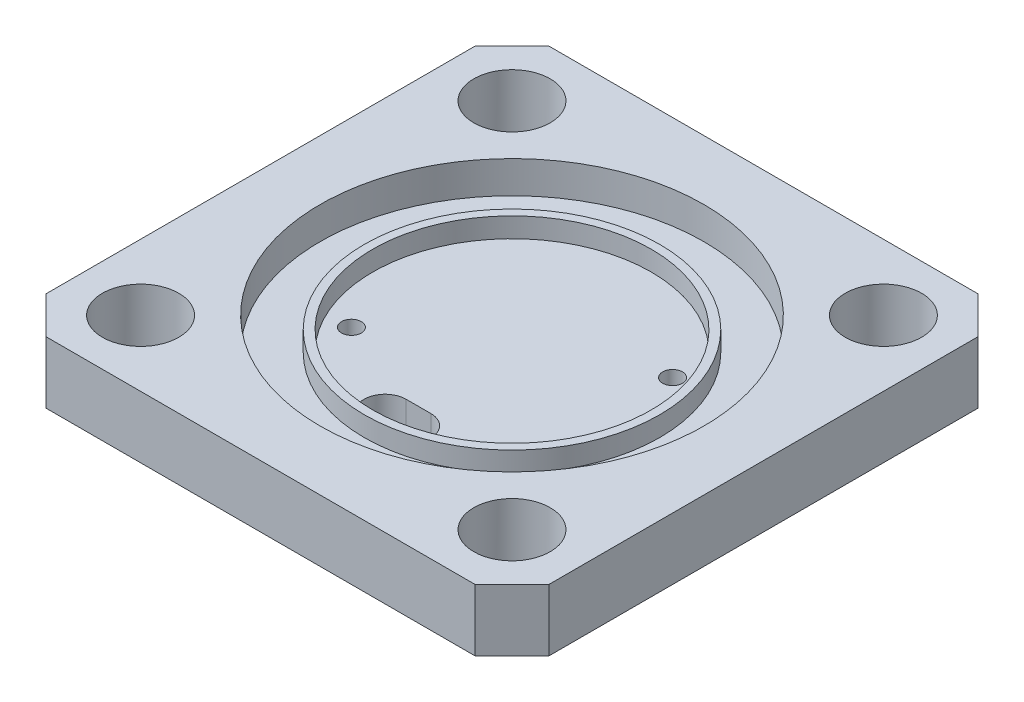
SolidWorks part; units mm, degrees
ref_plane "Front Plane" through (0, 0, 0) normal (0, 0, 1) x (1, 0, 0)
ref_plane "Top Plane" through (0, 0, 0) normal (0, 1, 0) x (1, 0, 0)
ref_plane "Right Plane" through (0, 0, 0) normal (1, 0, 0) x (0, 0, -1)
sketch "Sketch1" plane through (0, 0, 0) normal (0, 1, 0) x (1, 0, 0)
  line L1 (-20.32, -20.32) -> (20.32, -20.32)
  line L2 (-20.32, -20.32) -> (-20.32, 20.32)
  line L3 (-20.32, 20.32) -> (20.32, 20.32)
  line L4 (20.32, -20.32) -> (20.32, 20.32)
  line L5 (-20.32, -20.32) -> (20.32, 20.32) construction
  line L6 (-20.32, 20.32) -> (20.32, -20.32) construction
  point P0 (0, 0)
  dimension "D1" = 40.64
  dimension "D2" = 40.64
extrude "Boss-Extrude1" add sketch "Sketch1" along normal blind 5
sketch "Sketch2" plane through (0, 5, 0) normal (0, 1, 0) x (1, 0, 0)
  line L1 (-15, -15) -> (15, -15) construction
  line L2 (-15, -15) -> (-15, 15) construction
  line L3 (-15, 15) -> (15, 15) construction
  line L4 (15, -15) -> (15, 15) construction
  line L5 (-15, -15) -> (15, 15) construction
  line L6 (-15, 15) -> (15, -15) construction
  circle A0 centre (-15, 15) radius 3.085
  circle A1 centre (15, 15) radius 3.085
  circle A2 centre (15, -15) radius 3.085
  circle A3 centre (-15, -15) radius 3.085
  point P0 (0, 0)
  dimension "D3" = 6.17
  dimension "D1" = 30
  dimension "D2" = 30
  dimension "D4" = 2
  dimension "D5" = 2
extrude "Cut-Extrude1" cut sketch "Sketch2" against normal up to next contours A0 | A1 | A2 | A3
chamfer "Chamfer1" distance 3 angle 45 4 edges at (-20.32, 2.5, 20.32) (20.32, 2.5, 20.32) (20.32, 2.5, -20.32) (-20.32, 2.5, -20.32)
sketch "Sketch3" plane through (0, 5, 0) normal (0, 1, 0) x (1, 0, 0)
  circle A0 centre (0, 0) radius 11.25
  dimension "D1" = 22.5
extrude "Cut-Extrude2" cut sketch "Sketch3" against normal blind 2.6
ref_point "Point1"
sketch "Sketch4" plane through (0, 5, 0) normal (0, 1, 0) x (1, 0, 0)
  circle A0 centre (0, 0) radius 12000
  circle A1 centre (0, 0) radius 15.5
  circle A2 centre (0, 0) radius 11.925
  dimension "D1" = 24000
  dimension "D2" = 31
  dimension "D3" = 23.85
extrude "Cut-Extrude3" cut sketch "Sketch4" against normal blind 2.6 contours A1 A2 region at (-15.0616, 5, 0)
sketch "Sketch5" plane through (0, 2.4, 0) normal (0, 1, 0) x (1, 0, 0)
  line L0 (0, 0) -> (0, -11.25) construction
  line L1 (-1, -9.25) -> (1, -9.25) construction
  line L2 (-1, -11.25) -> (1, -11.25) construction
  line L3 (-1, -11.25) -> (-1, -7.25) construction
  line L4 (-1, -7.25) -> (1, -7.25) construction
  line L5 (1, -11.25) -> (1, -7.25) construction
  line L6 (-1, -11.25) -> (1, -7.25) construction
  line L7 (-1, -7.25) -> (1, -11.25) construction
  line L8 (-1, -7.55) -> (1, -7.55)
  line L9 (-1, -10.95) -> (1, -10.95)
  circle A0 centre (0, 0) radius 11.25 construction
  circle A1 centre (0, 0) radius 9.25 construction
  arc A2 (-1, -7.55) -> (-1, -10.95) centre (-1, -9.25) ccw
  arc A7 (1, -10.95) -> (1, -7.55) centre (1, -9.25) ccw
  point P6 (0, -9.25)
  point P14 (0, -9.25)
  dimension "D1" = 4
  dimension "D2" = 2
  dimension "D3" = 0
  dimension "D4" = 3.4
extrude "Cut-Extrude4" cut sketch "Sketch5" against normal through all contours L9 A7 L8 A2
sketch "Sketch6" plane through (0, 5, 0) normal (0, 1, 0) x (1, 0, 0)
  circle A3 centre (0, 0) radius 11.25 construction
  circle A4 centre (0, 0) radius 11.25
  circle A5 centre (0, 0) radius 11.925
  circle A8 centre (0, 0) radius 11.925
  dimension "D1" = 0
extrude "Cut-Extrude5" cut sketch "Sketch6" against normal blind 1
sketch "Sketch7" plane through (0, 2.4, 0) normal (0, 1, 0) x (1, 0, 0)
  line L0 (8.2431, 4.7273) -> (-8.2431, -4.7273) construction
  circle A0 centre (8.2431, 4.7273) radius 0.8
  circle A1 centre (0, 0) radius 11.25
  circle A2 centre (0, 0) radius 11.25 construction
  circle A3 centre (8.2431, 4.7273) radius 1
  circle A4 centre (8.2431, 4.7273) radius 1 construction
  circle A5 centre (-8.2431, -4.7273) radius 1
  circle A6 centre (-8.2431, -4.7273) radius 1 construction
  circle A7 centre (0, 0) radius 11
  circle A8 centre (0, 0) radius 11 construction
  circle A9 centre (-8.2431, -4.7273) radius 0.8
  dimension "D5" = 1.6
  dimension "D6" = 1.6
  dimension "D1" = 0
  dimension "D2" = 0
  dimension "D3" = 0
  dimension "D4" = 0
extrude "Cut-Extrude6" cut sketch "Sketch7" against normal through all contours A9 | A0 | A0 region at (8.2431, 2.4, -4.7273) region at (-8.2431, 2.4, 4.7273)
